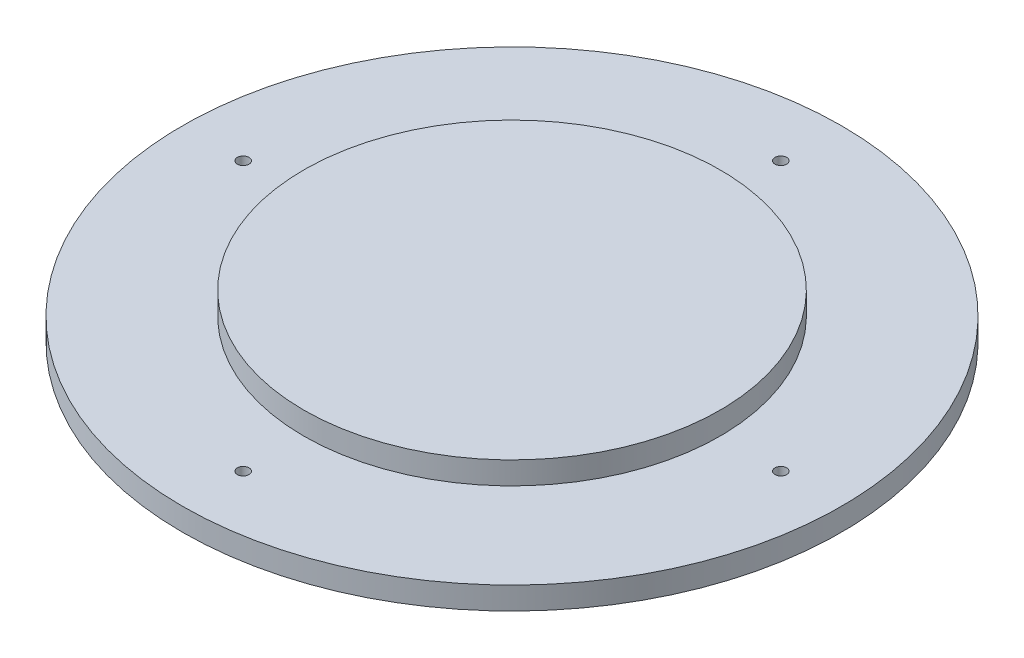
SolidWorks part; units mm, degrees
ref_plane "Plan de face" through (0, 0, 0) normal (0, 0, 1) x (1, 0, 0)
ref_plane "Plan de dessus" through (0, 0, 0) normal (0, 1, 0) x (1, 0, 0)
ref_plane "Plan de droite" through (0, 0, 0) normal (1, 0, 0) x (0, 0, -1)
sketch "Esquisse1" plane through (0, 0, 0) normal (0, 1, 0) x (1, 0, 0)
  circle A0 centre (0, 0) radius 84.1225
  dimension "D1" = 168.245
extrude "Boss.-Extru.1" add sketch "Esquisse1" against normal blind 5.75
sketch "Esquisse2" plane through (0, 0, 0) normal (0, 1, 0) x (1, 0, 0)
  circle A0 centre (0, 0) radius 53.13
  dimension "D1" = 106.26
extrude "Boss.-Extru.2" add sketch "Esquisse2" along normal blind 5.75
sketch "Esquisse3" plane through (0, 0, 0) normal (0, 1, 0) x (1, 0, 0)
  line L0 (0, 68.6225) -> (0, 84.1225) construction
  line L1 (-68.6225, 0) -> (-84.1225, 0) construction
  line L2 (68.6225, 0) -> (84.1225, 0) construction
  line L3 (0, -68.6225) -> (0, -84.1225) construction
  circle A1 centre (-68.6225, 0) radius 1.5
  circle A2 centre (0, -68.6225) radius 1.5
  circle A3 centre (0, 68.6225) radius 1.5
  circle A4 centre (68.6225, 0) radius 1.5
  circle A5 centre (0, 0) radius 84.1225 construction
  dimension "D1" = 15.5
  dimension "D2" = 15.5
  dimension "D3" = 15.5
  dimension "D4" = 15.5
extrude "Enlèv. mat.-Extru.1" cut sketch "Esquisse3" against normal blind 5 contours A1 | A4 | A2 | A3
